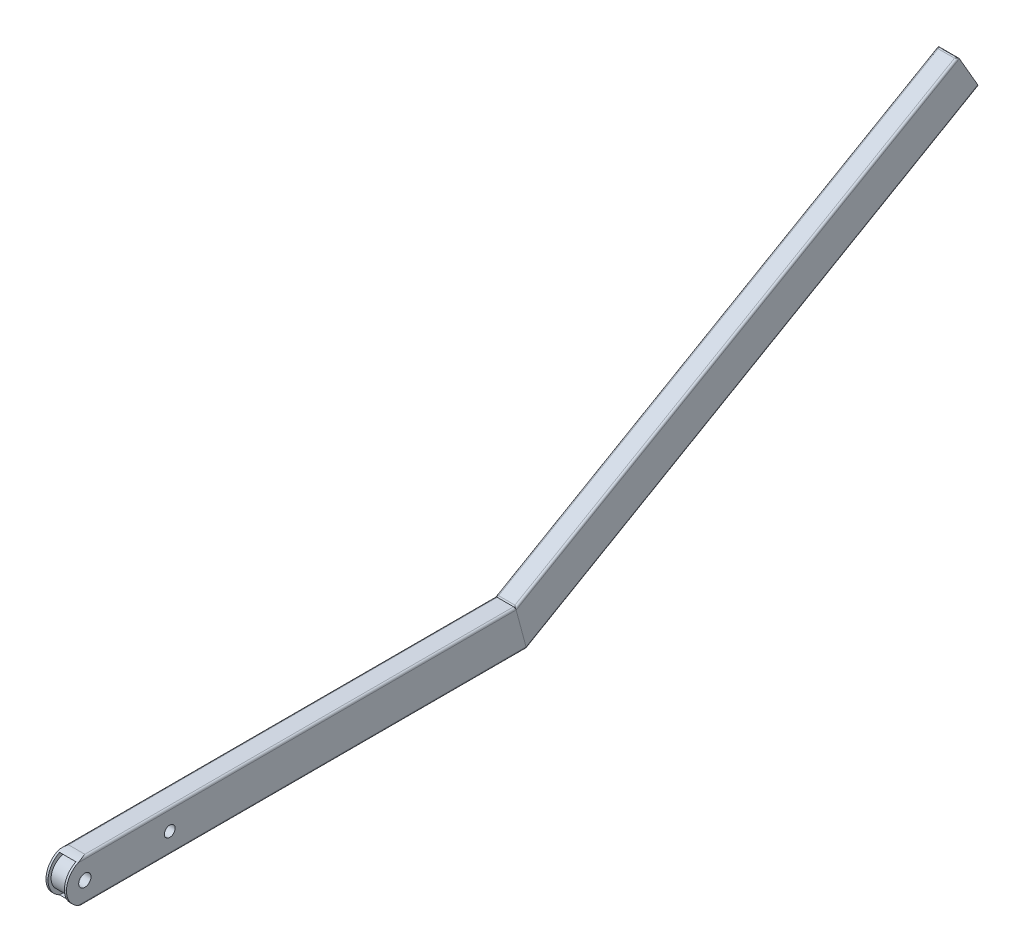
SolidWorks part; units mm, degrees
material "C40 or 38NiCrMo4"
ref_plane "Piano frontale" through (0, 0, 0) normal (0, 0, 1) x (1, 0, 0)
ref_plane "Piano superiore" through (0, 0, 0) normal (0, 1, 0) x (1, 0, 0)
ref_plane "Piano destro" through (0, 0, 0) normal (1, 0, 0) x (0, 0, -1)
sketch "Schizzo1" plane through (0, 0, 0) normal (0, 0, 1) x (1, 0, 0)
  line L1 (2, 0) -> (18, 0)
  line L2 (0, 2) -> (0, 38)
  line L3 (2, 40) -> (18, 40)
  line L4 (20, 2) -> (20, 38)
  arc A0 (2, 0) -> (0, 2) centre (2, 2) cw
  arc A1 (18, 0) -> (20, 2) centre (18, 2) ccw
  arc A2 (18, 40) -> (20, 38) centre (18, 38) cw
  arc A3 (0, 38) -> (2, 40) centre (2, 38) cw
  point P7 (0, 0)
  point P10 (20, 0)
  point P15 (0, 40)
  dimension "D3" = 2
  dimension "D1" = 40
  dimension "D2" = 20
extrude "Estrusione-Sottile1" add sketch "Schizzo1" along normal blind 450 thin
sketch "Schizzo2" plane through (2, 0, 0) normal (1, 0, 0) x (0, 0, -1)
  line L0 (-1450, 20) -> (48550, 20) construction
  line L1 (-450, 2) -> (-450, 38) construction
  circle A0 centre (-432, 20) radius 15
  point P5 (-450, 20)
  dimension "D1" = 18
  dimension "D2" = 30
extrude "Estrusione-Estrusione1" add sketch "Schizzo2" along normal up to surface (16 mm away) up to face at (18, 20, 225)
pattern_linear "Ripetizione a L1" count 2 spacing 83 along (0, 0, -1) of "Estrusione-Estrusione1"
sketch "Schizzo3" plane through (20, 0, 0) normal (1, 0, 0) x (0, 0, -1)
  line L0 (-1450, 20) -> (48550, 20) construction
  line L1 (-450, 2) -> (-450, 38) construction
  circle A0 centre (-432, 20) radius 6
  circle A1 centre (-349, 20) radius 5.25
  point P5 (-450, 20)
  dimension "D1" = 12
  dimension "D2" = 10.5
  dimension "D3" = 18
  dimension "D4" = 83
extrude "Taglio-Estrusione1" cut sketch "Schizzo3" against normal through all
sketch "Schizzo4" plane through (20, 0, 0) normal (1, 0, 0) x (0, 0, -1)
  line L0 (0, 0) -> (-10.718, 40)
  line L1 (-450, 40) -> (0, 40) construction
  line L2 (-10.718, 40) -> (0, 40)
  line L3 (0, 40) -> (0, 0)
  dimension "D1" = 15
extrude "Taglio-Estrusione2" cut sketch "Schizzo4" against normal through all
fillet "Raccordo1" radius 20 2 edges at (10, 0, 450) (10, 40, 450)
ref_plane "Piano1" through (10, 0, 0) normal (1, 0, 0) x (0, 0, -1)
sketch "Schizzo5" plane through (10, 0, 0) normal (1, 0, 0) x (0, 0, -1)
  line L0 (-5.359, 20) -> (489.2689, 305.5735) construction
  line L1 (-10.1821, 38) -> (-0.5359, 2) construction
  line L2 (-5.359, 20) -> (-119.2678, 20) construction
  line L3 (422.2947, 290) -> (442.2947, 255.359)
  line L4 (442.2947, 255.359) -> (0, 0)
  line L5 (0, 0) -> (-10.718, 40)
  line L6 (-430, 40) -> (-10.718, 40) construction
  line L7 (-10.718, 40) -> (422.2947, 290)
  point P8 (432.2947, 272.6795)
  dimension "D1" = 150
  dimension "D2" = 500
extrude "Estrusione-Estrusione2" add sketch "Schizzo5" along normal mid plane 20 separate body
fillet "Raccordo2" radius 2 6 edges at (10, 290, -422.2947) (20, 165, -205.7884) (10, 40, 10.718) (0, 165, -205.7884) (20, 127.6795, -221.1474) (0, 127.6795, -221.1474)
sketch "Schizzo7" plane through (0, 255.359, -442.2947) normal (0, 0.5, -0.866) x (-1, 0, 0)
  line L0 (0, 2) -> (0, 38) construction
  line L1 (-18, 38) -> (-2, 38)
  line L2 (-18, 38) -> (-18, 2)
  line L3 (-18, 2) -> (-2, 2)
  line L4 (-2, 38) -> (-2, 2)
  line L5 (-18, 38) -> (-2, 2) construction
  line L6 (-18, 2) -> (-2, 38) construction
  line L7 (-2, 40) -> (-18, 40) construction
  line L8 (-18, 0) -> (-2, 0) construction
  line L9 (-20, 2) -> (-20, 38) construction
  point P0 (-10, 20)
  dimension "D1" = 2
  dimension "D2" = 2
  dimension "D3" = 2
  dimension "D4" = 2
extrude "Taglio-Estrusione3" cut sketch "Schizzo7" against normal through all both and the other way through all
